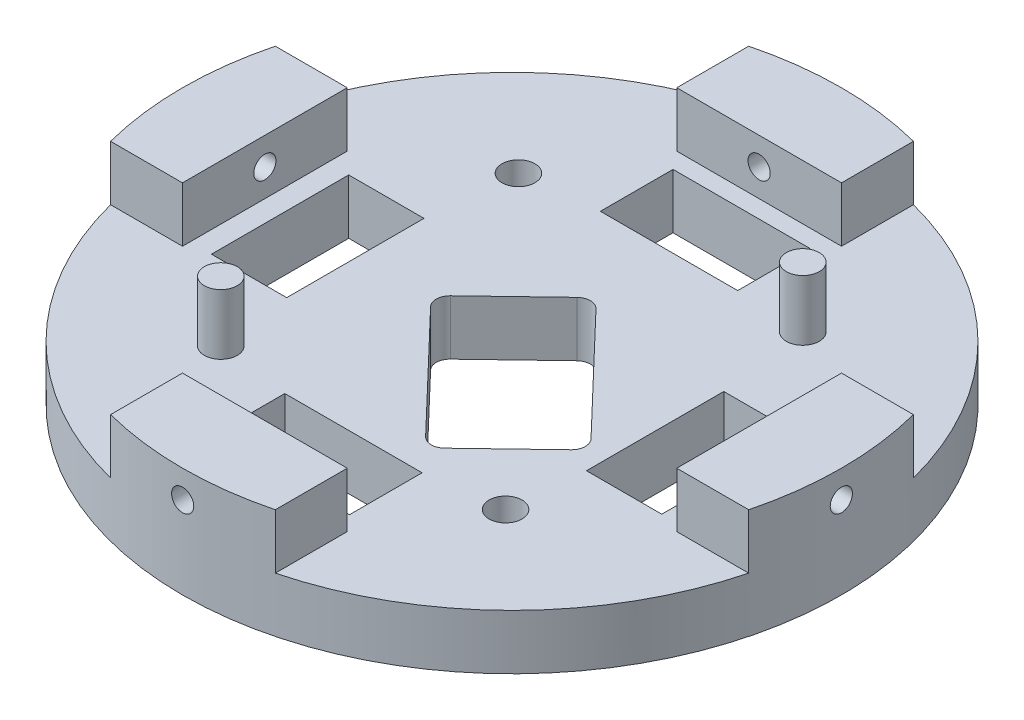
SolidWorks part; units mm, degrees
ref_plane "Front Plane" through (0, 0, 0) normal (0, 0, 1) x (1, 0, 0)
ref_plane "Top Plane" through (0, 0, 0) normal (0, 1, 0) x (1, 0, 0)
ref_plane "Right Plane" through (0, 0, 0) normal (1, 0, 0) x (0, 0, -1)
sketch "Sketch1" plane through (0, 0, 0) normal (0, 1, 0) x (1, 0, 0)
  circle A0 centre (0, 0) radius 76.2
  dimension "D1" = 152.4
extrude "Boss-Extrude1" add sketch "Sketch1" along normal blind 12.7
sketch "Sketch2" plane through (0, 12.7, 0) normal (0, 1, 0) x (1, 0, 0)
  line L9 (-19.05, -73.7803) -> (-19.05, -57.15)
  line L10 (-19.05, -57.15) -> (19.05, -57.15)
  line L11 (19.05, -57.15) -> (19.05, -73.7803)
  circle A0 centre (0, 0) radius 76.2 construction
  arc A1 (-19.05, -73.7803) -> (19.05, -73.7803) centre (0, 0) ccw
  point P20 (0, -57.15)
  dimension "D1" = 57.15
  dimension "D7" = 38.1
sketch "Sketch3" plane through (0, 12.7, 0) normal (0, 1, 0) x (1, 0, 0)
  point P0 (0, 0)
sketch "Sketch8" plane through (0, 12.7, 0) normal (0, 1, 0) x (1, 0, 0)
  arc A0 (-73.8992, 18.5835) -> (-73.6583, -19.5165) centre (0, 0) cw
sketch "Sketch9" plane through (0, 12.7, 0) normal (0, 1, 0) x (1, 0, 0)
  line L0 (34.52, 14.4543) -> (51.9245, 14.4543)
  line L1 (-52.2134, 14.4543) -> (-34.8089, 14.4543)
  line L2 (-52.2134, 14.4543) -> (-52.2134, -17.2957)
  line L3 (-52.2134, -17.2957) -> (-34.8089, -17.2957)
  line L4 (-34.8089, 14.4543) -> (-34.8089, -17.2957)
  line L5 (-15.8287, 53.0617) -> (15.9213, 53.0617)
  line L6 (-15.8287, 53.0617) -> (-15.8287, 36.2685)
  line L7 (-15.8287, 36.2685) -> (15.9213, 36.2685)
  line L8 (15.9213, 53.0617) -> (15.9213, 36.2685)
  line L9 (34.52, 14.4543) -> (34.52, -17.2957)
  line L10 (34.52, -17.2957) -> (51.9245, -17.2957)
  line L11 (51.9245, 14.4543) -> (51.9245, -17.2957)
  line L12 (-15.8287, -36.7093) -> (15.9213, -36.7093)
  line L13 (-15.8287, -36.7093) -> (-15.8287, -53.5025)
  line L14 (-15.8287, -53.5025) -> (15.9213, -53.5025)
  line L15 (15.9213, -36.7093) -> (15.9213, -53.5025)
  dimension "D1" = 31.75
  dimension "D2" = 31.75
extrude "Cut-Extrude1" cut sketch "Sketch9" against normal blind 12.7 contours L12 L15 L14 L13 | L0 L11 L10 L9 | L7 L8 L5 L6 | L1 L4 L3 L2
sketch "Sketch12" plane through (0, 12.7, 0) normal (0, 1, 0) x (1, 0, 0)
  circle A0 centre (-32.9232, 34.4123) radius 3.81
  circle A1 centre (32.9232, -34.4123) radius 3.81
  dimension "D1" = 7.62
  dimension "D2" = 95.25
  dimension "D3" = 180
  dimension "D4" = 47.625
extrude "Cut-Extrude7" cut sketch "Sketch12" against normal through all contours A1 | A0
sketch "Sketch14" plane through (0, 12.7, 0) normal (0, 1, 0) x (1, 0, 0)
  circle A0 centre (31.7143, 35.5295) radius 3.81
  circle A1 centre (-32.7613, -34.5809) radius 3.81
  dimension "D1" = 7.62
  dimension "D2" = 7.62
  dimension "D3" = 95.25
  dimension "D4" = 47.625
extrude "Boss-Extrude5" add sketch "Sketch14" along normal blind 13.97
extrude "Boss-Extrude6" add sketch "Sketch2" along normal blind 12.7 contours L10 L11 A1 L9
sketch "Sketch15" plane through (0, 0, 57.15) normal (0, 0, -1) x (-1, 0, 0)
  line L4 (-19.05, 25.4) -> (-19.05, 12.7) construction
  line L5 (19.05, 25.4) -> (-19.05, 25.4) construction
  circle A0 centre (0, 19.05) radius 2.5654
  point P6 (-19.05, 19.05)
  point P13 (0, 25.4)
  dimension "D1" = 5.1308
  dimension "D2" = 19.05
  dimension "D3" = 6.35
extrude "Cut-Extrude8" cut sketch "Sketch15" against normal through all
ref_axis "Axis1" through (0, 28.0035, 0) along (0, -1, 0)
pattern_circular "CirPattern1" count 4 over 360 about axis through (0, 28.0035, 0) along (0, -1, 0) of "Boss-Extrude6", "Cut-Extrude8"
sketch "Sketch17" plane through (0, 12.7, 0) normal (0, 1, 0) x (1, 0, 0)
  line L0 (-32.9232, 34.4123) -> (32.9232, -34.4123) construction
  line L1 (-18.5526, -0.1736) -> (11.2977, -31.374)
  line L2 (-18.5526, -0.1736) -> (0.9936, 18.5268)
  line L3 (11.2977, -31.374) -> (30.8439, -12.6737)
  line L4 (0.9936, 18.5268) -> (30.8439, -12.6737)
  point P4 (21.0708, -22.0239)
  dimension "D1" = 43.18
  dimension "D2" = 12.7
  dimension "D3" = 27.051
extrude "Cut-Extrude9" cut sketch "Sketch17" against normal through all contours L2 L4 L3 L1
fillet "Fillet1" radius 3.175 4 edges at (11.2977, 6.35, 31.374) (30.8439, 6.35, 12.6737) (0.9936, 6.35, -18.5268) (-18.5526, 6.35, 0.1736)
equation "\"D2@Sketch15\"=1.5/2"
equation "\"D3@Sketch15\"=0.5/2"
